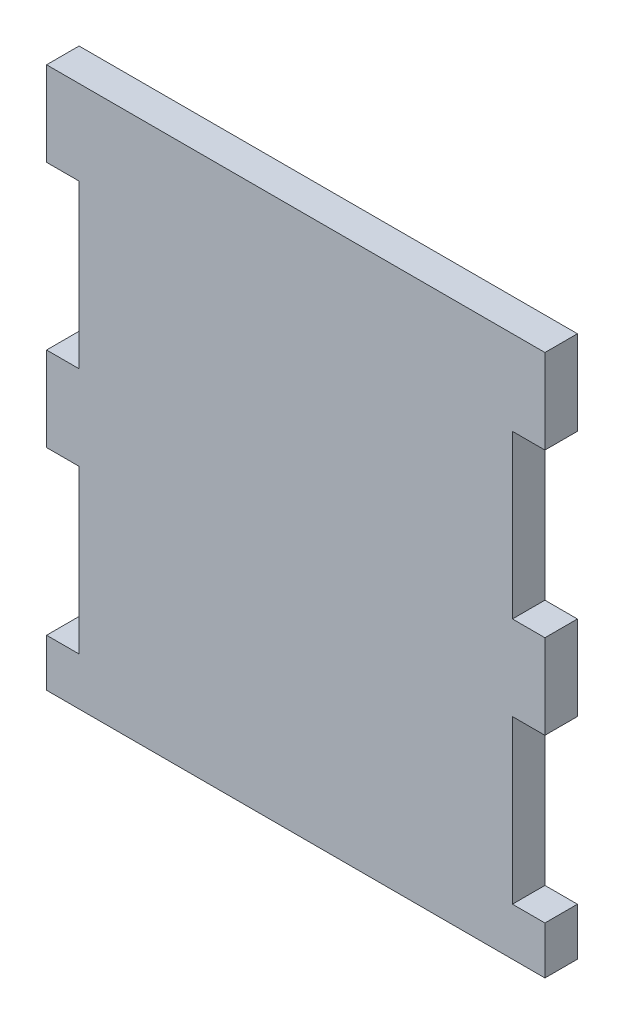
SolidWorks part; units mm, degrees
material "Oak"
ref_plane "Front Plane" through (0, 0, 0) normal (0, 0, 1) x (1, 0, 0)
ref_plane "Top Plane" through (0, 0, 0) normal (0, 1, 0) x (1, 0, 0)
ref_plane "Right Plane" through (0, 0, 0) normal (1, 0, 0) x (0, 0, -1)
sketch "Sketch1" plane through (0, 0, 0) normal (0, 0, 1) x (1, 0, 0)
  line L1 (-40.9935, 16.542) -> (5.0065, 16.542)
  line L2 (-40.9935, 16.542) -> (-40.9935, -33.458)
  line L3 (-40.9935, -33.458) -> (5.0065, -33.458)
  line L4 (5.0065, 16.542) -> (5.0065, -33.458)
  dimension "D1" = 50
  dimension "D2" = 46
extrude "Boss-Extrude1" add sketch "Sketch1" along normal blind 3
sketch "Sketch2" plane through (0, 0, 3) normal (0, 0, 1) x (1, 0, 0)
  line L0 (-40.9935, 16.542) -> (-40.9935, -33.458) construction
  line L1 (-40.9935, 8.742) -> (-37.9935, 8.742)
  line L2 (-40.9935, 8.742) -> (-40.9935, -6.258)
  line L3 (-40.9935, -6.258) -> (-37.9935, -6.258)
  line L4 (-37.9935, 8.742) -> (-37.9935, -6.258)
  line L5 (5.0065, 16.542) -> (-40.9935, 16.542) construction
  line L6 (5.0065, -33.458) -> (5.0065, 16.542) construction
  line L7 (5.0065, 8.742) -> (2.0065, 8.742)
  line L8 (5.0065, 8.742) -> (5.0065, -6.258)
  line L9 (5.0065, -6.258) -> (2.0065, -6.258)
  line L10 (2.0065, 8.742) -> (2.0065, -6.258)
  point P8 (-39.4935, 8.742)
  dimension "D1" = 3
  dimension "D2" = 7.8
  dimension "D3" = 15
  dimension "D4" = 3
  dimension "D5" = 7.8
  dimension "D6" = 15
extrude "Cut-Extrude1" cut sketch "Sketch2" against normal through all
pattern_linear "LPattern1" count 3 spacing 22.8 along (0, -1, 0) of "Cut-Extrude1"
